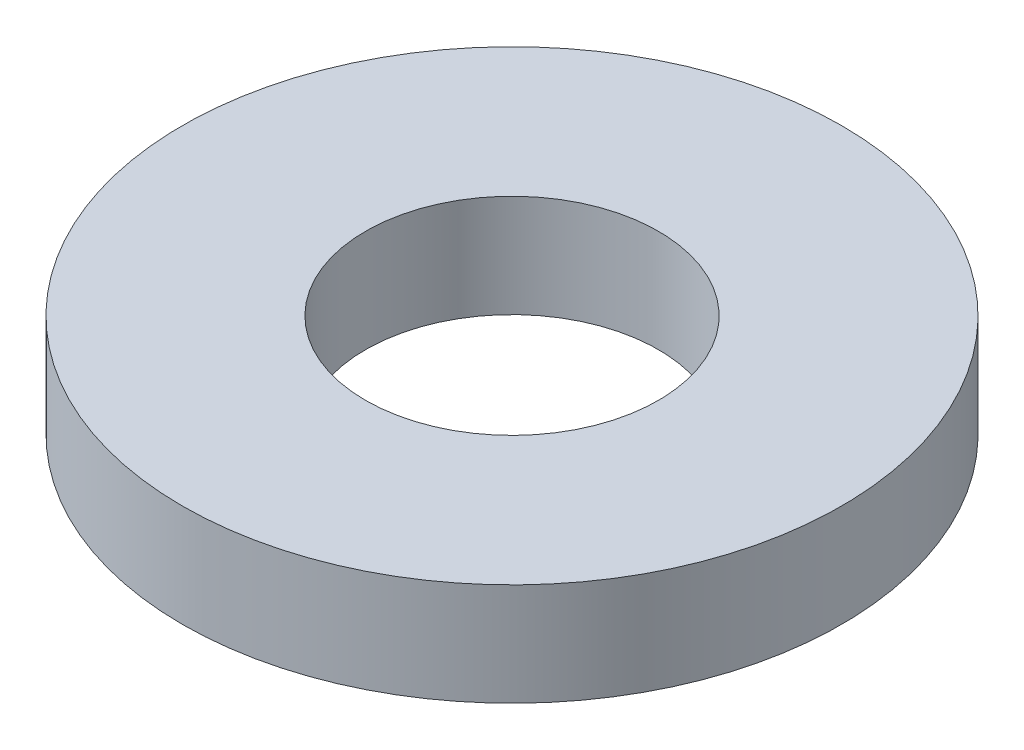
SolidWorks part; units mm, degrees
ref_plane "Front Plane" through (0, 0, 0) normal (0, 0, 1) x (1, 0, 0)
ref_plane "Top Plane" through (0, 0, 0) normal (0, 1, 0) x (1, 0, 0)
ref_plane "Right Plane" through (0, 0, 0) normal (1, 0, 0) x (0, 0, -1)
sketch "Sketch1" plane through (0, 0, 0) normal (0, 1, 0) x (1, 0, 0)
  circle A0 centre (0, 0) radius 90
  dimension "FLANGE_OD" = 180
extrude "Boss-Extrude1" add sketch "Sketch1" along normal blind 28
sketch "Sketch2" plane through (0, 0, 0) normal (0, 1, 0) x (1, 0, 0)
  circle A0 centre (0, 0) radius 40
  dimension "BORE_D" = 80
extrude "Cut-Extrude1" cut sketch "Sketch2" along normal through all
sketch "Sketch3" plane through (0, 28, 0) normal (0, 1, 0) x (1, 0, 0)
  circle A0 centre (0, 0) radius 30.1978 construction
  circle A1 centre (-30.1978, 0) radius 8.2888
  dimension "BOLT_D" = 16.5776
  dimension "BOLT_PCD" = 60.3956
extrude "Cut-Extrude2" cut sketch "Sketch3" against normal blind 19.4963 rebuild error yes
pattern_circular "CirPattern1" count 4 over 360 rebuild error yes
